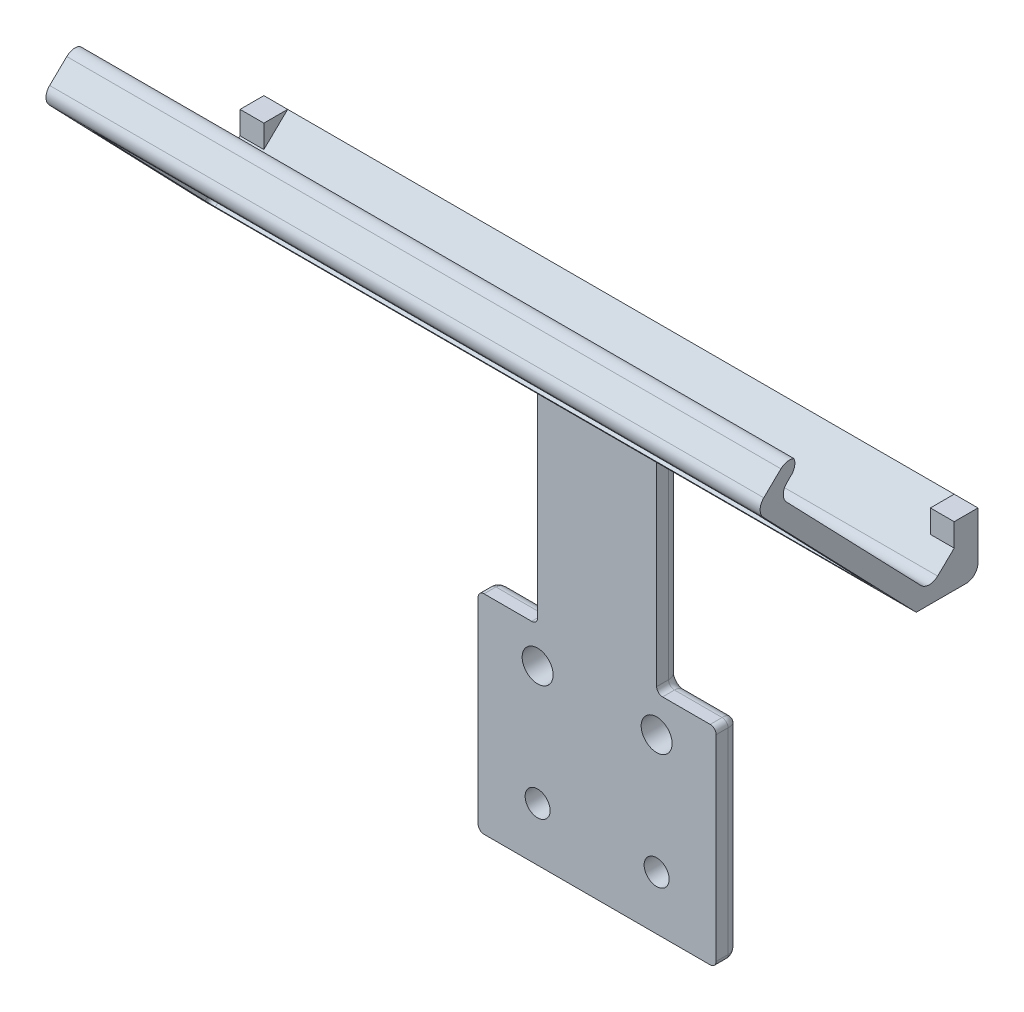
SolidWorks part; units mm, degrees
ref_plane "前视基准面" through (0, 0, 0) normal (0, 0, 1) x (1, 0, 0)
ref_plane "上视基准面" through (0, 0, 0) normal (0, 1, 0) x (1, 0, 0)
ref_plane "右视基准面" through (0, 0, 0) normal (1, 0, 0) x (0, 0, -1)
sketch "草图1" plane through (0, 0, 0) normal (0, 0, 1) x (1, 0, 0)
  line L0 (-20, 19) -> (-20, -16)
  line L1 (0, 0) -> (0, 24.0907) construction
  line L2 (0, 0) -> (37.3049, 0) construction
  line L3 (-20, -16) -> (20, -16)
  line L4 (-20, 19) -> (20, 19)
  line L5 (0, 0) -> (-37.3049, 0) construction
  line L6 (20, 19) -> (20, -16)
  circle A0 centre (-10, 13) radius 2.6
  circle A1 centre (-10, -7) radius 2.1
  circle A2 centre (10, -7) radius 2.1
  circle A3 centre (10, 13) radius 2.6
  point P21 (0, 19)
  point P22 (0, -16)
  dimension "D3" = 5.2
  dimension "D4" = 4.2
  dimension "D1" = 35
  dimension "D2" = 13
  dimension "D5" = 20
  dimension "D6" = 19
  dimension "D7" = 10
  dimension "D8" = 10
  dimension "D9" = 20
extrude "凸台-拉伸1" add sketch "草图1" along normal blind 4
sketch "草图2" plane through (0, 19, 0) normal (0, 1, 0) x (1, 0, 0)
  line L0 (0, 4.0727) -> (0, -8.9557) construction
  line L1 (10, 0) -> (-10, 0)
  line L2 (20, 0) -> (-20, 0) construction
  line L3 (-10, 0) -> (-10, -4)
  line L4 (20, -4) -> (-20, -4) construction
  line L5 (-10, -4) -> (10, -4)
  line L6 (10, 0) -> (10, -4)
  point P12 (0, -4)
  point P13 (0, 0)
  dimension "D1" = 10
extrude "凸台-拉伸2" add sketch "草图2" along normal blind 50
fillet "圆角1" radius 1 6 edges at (20, -16, 2) (-20, -16, 2) (20, 19, 2) (10, 19, 2) (-10, 19, 2) (-20, 19, 2)
sketch "草图3" plane through (0, 0, 0) normal (0, 0, 1) x (1, 0, 0)
  line L0 (0, 82.1866) -> (0, -12.2597) construction
  line L1 (-56, 69) -> (56, 69)
  line L2 (-56, 69) -> (-56, 59)
  line L3 (-56, 59) -> (56, 59)
  line L4 (-10, 69) -> (10, 69) construction
  line L5 (56, 69) -> (56, 59)
  point P12 (0, 59)
  point P13 (0, 69)
  dimension "D1" = 56
  dimension "D2" = 10
extrude "凸台-拉伸4" add sketch "草图3" along normal blind 4
sketch "草图5" plane through (-56, 0, 0) normal (-1, 0, 0) x (0, 0, 1)
  line L0 (0, 69) -> (4, 65.1464)
  line L1 (4, 65.1464) -> (4, 69)
  line L2 (4, 69) -> (0, 69)
  line L3 (4, 69) -> (4, 59) construction
extrude "切除-拉伸1" cut sketch "草图5" against normal through all
sketch "草图6" plane through (-56, 0, 0) normal (-1, 0, 0) x (0, 0, 1)
  line L0 (0, 69) -> (0, 59)
  line L1 (0, 59) -> (4, 59)
  line L2 (4, 59) -> (4, 69)
  line L3 (4, 69) -> (0, 69)
extrude "凸台-拉伸5" add sketch "草图6" along normal blind 4
sketch "草图9" plane through (56, 0, 0) normal (1, 0, 0) x (0, 0, -1)
  line L0 (0, 69) -> (-4, 69)
  line L1 (-4, 69) -> (-4, 59)
  line L2 (-4, 59) -> (0, 59)
  line L3 (0, 59) -> (0, 69)
extrude "凸台-拉伸8" add sketch "草图9" along normal blind 4
ref_plane "基准面4" through (-56, 0, 0) normal (-1, 0, 0) x (0, 0, 1)
sketch "草图10" plane through (-60, 0, 0) normal (-1, 0, 0) x (0, 0, 1)
  line L0 (0, 59) -> (10.3799, 59)
  line L3 (0, 69) -> (0, 59)
  line L4 (0, 69) -> (10.3799, 59)
extrude "凸台-拉伸9" add sketch "草图10" against normal up to surface (120 mm away) up to face at (60, 64, 2)
sketch "草图11" plane through (-60, 0, 0) normal (-1, 0, 0) x (0, 0, 1)
  line L0 (10.3799, 59) -> (8.2194, 61.0814)
  line L1 (10.3799, 59) -> (4, 65.1464) construction
  line L2 (8.2194, 61.0814) -> (35.2778, 89.1678)
  line L3 (35.2778, 89.1678) -> (37.4383, 87.0863)
  line L4 (37.4383, 87.0863) -> (10.3799, 59)
  dimension "D1" = 39
  dimension "D2" = 3
extrude "凸台-拉伸10" add sketch "草图11" against normal up to surface (120 mm away) up to face at (60, 64.2293, 3.676)
sketch "草图12" plane through (0, 25.2957, -26.2566) normal (0, 0.6938, -0.7202) x (-1, 0, 0)
  line L0 (-60, 88.6912) -> (60, 88.6912)
  line L1 (60, 88.6912) -> (60, 86.1912)
  line L2 (60, 88.6912) -> (60, 49.6912) construction
  line L3 (60, 86.1912) -> (-60, 86.1912)
  line L4 (-60, 88.6912) -> (-60, 49.6912) construction
  line L5 (-60, 86.1912) -> (-60, 88.6912)
  dimension "D1" = 2.5
extrude "凸台-拉伸11" add sketch "草图12" along normal blind 5
fillet "圆角2" radius 2 1 edges at (0, 87.0863, 37.4383)
fillet "圆角3" radius 2 2 edges at (10, 59, 2) (-10, 59, 2)
fillet "圆角4" radius 2 17 edges at (-10.5858, 58.4142, 0) (-10, 38.5, 0) (-10.2929, 19.2929, 0) (-15, 19, 0) (-19.7071, 18.7071, 0) (-20, 1.5, 0) (-19.7071, -15.7071, 0) (0, -16, 0) (19.7071, -15.7071, 0) (20, 1.5, 0) (19.7071, 18.7071, 0) (15, 19, 0) (10.2929, 19.2929, 0) (10, 38.5, 0) (10.5858, 58.4142, 0) (-36, 59, 0) (36, 59, 0)
fillet "圆角5" radius 2 1 edges at (0, 61.0814, 8.2194)
fillet "圆角6" radius 2 3 edges at (0, 92.6368, 31.677) (0, 90.8364, 29.9425) (0, 87.3673, 33.5433)
sketch "草图13" plane through (0, 23.2143, -24.0961) normal (0, -0.6938, 0.7202) x (1, 0, 0)
  line L8 (56, 53.6912) -> (56, 82.6912)
  line L9 (-56, 53.6912) -> (56, 53.6912)
  line L10 (56, 82.6912) -> (-56, 82.6912)
  line L11 (-56, 82.6912) -> (-56, 53.6912)
  line L12 (56, 53.6912) -> (56, 82.6912)
  line L13 (-56, 53.6912) -> (56, 53.6912)
  line L14 (56, 82.6912) -> (-56, 82.6912)
  line L15 (-56, 82.6912) -> (-56, 53.6912)
  dimension "D1" = 4
extrude "切除-拉伸2" cut sketch "草图13" against normal blind 10
fillet "圆角7" radius 1 4 edges at (56, 83.8061, 32.1952) (-56, 83.8061, 32.1952) (-56, 62.9214, 12.0749) (56, 62.9214, 12.0749)
